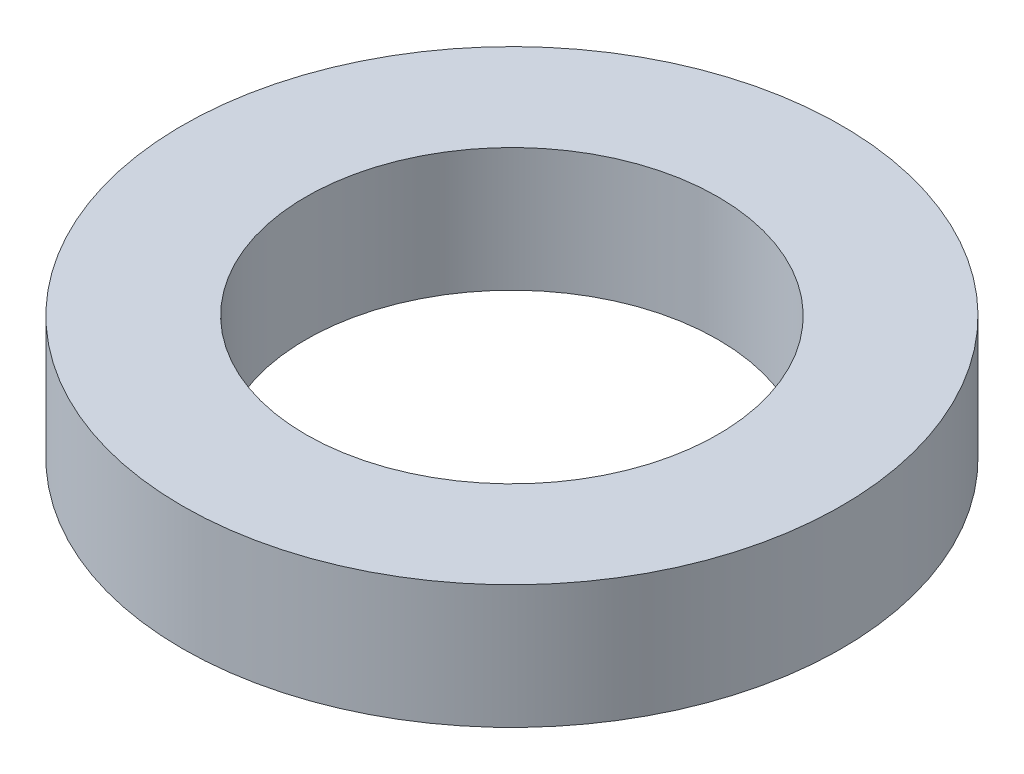
SolidWorks part; units mm, degrees
ref_plane "Front Plane" through (0, 0, 0) normal (0, 0, 1) x (1, 0, 0)
ref_plane "Top Plane" through (0, 0, 0) normal (0, 1, 0) x (1, 0, 0)
ref_plane "Right Plane" through (0, 0, 0) normal (1, 0, 0) x (0, 0, -1)
sketch "Sketch1" plane through (0, 0, 0) normal (0, 1, 0) x (1, 0, 0)
  circle A0 centre (0, 0) radius 80
  dimension "FLANGE_OD" = 160
extrude "Boss-Extrude1" add sketch "Sketch1" along normal blind 30
sketch "Sketch2" plane through (0, 0, 0) normal (0, 1, 0) x (1, 0, 0)
  circle A0 centre (0, 0) radius 50
  dimension "BORE_D" = 100
extrude "Cut-Extrude1" cut sketch "Sketch2" along normal through all
sketch "Sketch3" plane through (0, 30, 0) normal (0, 1, 0) x (1, 0, 0)
  circle A0 centre (0, 0) radius 35.9299 construction
  circle A1 centre (-35.9299, 0) radius 5.2007
  dimension "BOLT_D" = 10.4014
  dimension "BOLT_PCD" = 71.8597
extrude "Cut-Extrude2" cut sketch "Sketch3" against normal blind 29.9143 rebuild error yes
pattern_circular "CirPattern1" count 4 over 360 rebuild error yes
